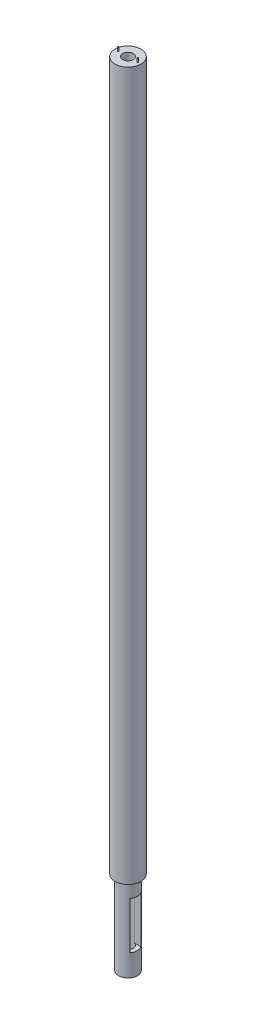
SolidWorks part; units mm, degrees
ref_plane "Front Plane" through (0, 0, 0) normal (0, 0, 1) x (1, 0, 0)
ref_plane "Top Plane" through (0, 0, 0) normal (0, 1, 0) x (1, 0, 0)
ref_plane "Right Plane" through (0, 0, 0) normal (1, 0, 0) x (0, 0, -1)
sketch "Sketch31" plane through (0, 0, 0) normal (0, 0, 1) x (1, 0, 0)
  line L0 (0, 0) -> (0, 35.4702)
sweep "Sweep3" add path "Sketch31" circular profile diameter 8 parameters "D3"=8
sketch "Sketch38" plane through (0, 0, 0) normal (0, 0, 1) x (1, 0, 0)
  line L1 (4, 35.4702) -> (-4, 35.4702) construction
  line L2 (0, 35.4702) -> (0, 336.2875)
sweep "Sweep4" add path "Sketch38" circular profile diameter 11 parameters "D3"=11
sketch "Sketch45" plane through (0, 0, 0) normal (0, 1, 0) x (1, 0, 0)
  circle A0 centre (0, 0) radius 2.25
extrude "Cut-Extrude2" cut sketch "Sketch45" along normal through all
sketch3d "3DSketch1"
  line L1 (0, 336.2875, 0) -> (0, 0, 0) construction
  line L2 (0, 336.2875, 0) -> (2.25, 336.2875, 0)
  line L18 (-5.5, 336.2875, 0) -> (-5.5, 336.2875, -5.5)
  line L19 (-5.5, 336.2875, -5.5) -> (0, 336.2875, -5.5)
  line L20 (0, 336.2875, -5.5) -> (5.5, 336.2875, -5.5)
  line L21 (5.5, 336.2875, -5.5) -> (5.5, 336.2875, 0)
  line L22 (0, 336.2875, 5.5) -> (5.5, 336.2875, 5.5)
  line L23 (5.5, 336.2875, 5.5) -> (5.5, 336.2875, 0)
  line L24 (0, 336.2875, 5.5) -> (-5.5, 336.2875, 5.5)
  line L25 (-5.5, 336.2875, 5.5) -> (-5.5, 336.2875, 0)
  circle A0 centre (0, 336.2875, 0) radius 2.25
  circle A1 centre (0, 336.2875, 0) radius 5.5 construction
  point P3 (0, 338.5375, 0)
  point P6 (0, 341.7875, 0)
  dimension "D1" = 5.5
  dimension "D3" = 5.5
  dimension "D2" = 5.5
  dimension "D4" = 5.5
  dimension "D5" = 5.5
  dimension "D6" = 5.5
  dimension "D7" = 5.5
  dimension "D8" = 5.5
sketch3d "3DSketch4"
  line L0 (4.125, 336.2875, 0) -> (4.125, 337.7875, 0)
  line L1 (-4.125, 336.2875, 0) -> (-4.125, 337.7875, 0)
  point P5 (-4.125, 336.2875, 0)
  point P6 (4.125, 336.2875, 0)
  dimension "D1" = 1.5
  dimension "D2" = 1.5
sweep "Sweep5" add path "3DSketch4" circular profile diameter 0.5 parameters "D3"=0.5
sketch3d "3DSketch5"
  line L0 (-4.125, 336.2875, 0) -> (-4.125, 337.7875, 0)
  line L1 (-5.5, 336.2875, 0) -> (-2.75, 336.2875, 0)
  line L2 (-4.125, 336.2875, 0) -> (-2.75, 336.2875, 0)
  dimension "D1" = 1.5
  dimension "D2" = 4.125
sweep "Sweep6" add path "3DSketch5" circular profile diameter 0.5 parameters "D3"=0.5
sketch "Sketch72" plane through (0, 0, 0) normal (1, 0, 0) x (0, 0, -1)
  line L0 (-2.318, 9.2361) -> (2.182, 9.2361)
  line L2 (-2.318, 9.2361) -> (-2.318, 29.2361)
  line L3 (-2.318, 29.2361) -> (2.182, 29.2361)
  line L4 (2.182, 29.2361) -> (2.182, 9.2361)
  dimension "D1" = 20
  dimension "D2" = 4.5
extrude "Cut-Extrude6" cut sketch "Sketch72" along normal blind 20
sketch "Sketch73" plane through (0, 0, 0) normal (0, 0, 1) x (1, 0, 0)
  line L0 (3.875, 337.7212) -> (4.3306, 337.589)
  line L1 (3.875, 337.7875) -> (3.875, 336.2875) construction
  point P2 (0, 0)
